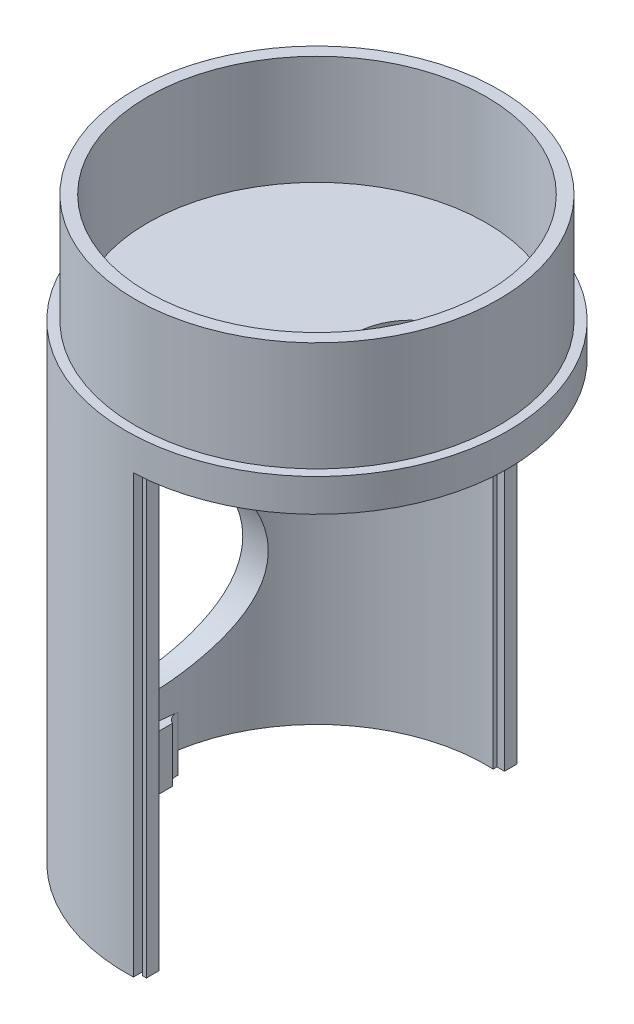
SolidWorks part; units mm, degrees
ref_plane "Front Plane" through (0, 0, 0) normal (0, 0, 1) x (1, 0, 0)
ref_plane "Top Plane" through (0, 0, 0) normal (0, 1, 0) x (1, 0, 0)
ref_plane "Right Plane" through (0, 0, 0) normal (1, 0, 0) x (0, 0, -1)
sketch "Sketch13" plane through (0, 0, 0) normal (0, 1, 0) x (1, 0, 0)
  line L0 (0, 0) -> (-19.6145, 0) construction
  line L28 (0.6552, 15.4861) -> (0.6552, 15.8306)
  line L29 (0.6552, 15.8306) -> (1.3406, 15.8306)
  line L30 (1.3406, 15.8306) -> (1.343, 16.9583)
  line L31 (1.343, 16.9583) -> (0.9998, 16.9583)
  line L32 (0.9998, 16.9583) -> (0.9998, 16.6614)
  line L33 (0.9998, 16.6614) -> (0.6704, 16.6614)
  line L34 (0.6704, 16.6614) -> (0.6704, 17.4872)
  line L35 (0.6704, -17.4872) -> (0.6704, -16.6614)
  line L36 (0.6704, -16.6614) -> (0.9998, -16.6614)
  line L37 (0.9998, -16.6614) -> (0.9998, -16.9583)
  line L38 (0.9998, -16.9583) -> (1.343, -16.9583)
  line L39 (1.343, -16.9583) -> (1.3406, -15.8306)
  line L40 (1.3406, -15.8306) -> (0.6552, -15.8306)
  line L41 (0.6552, -15.8306) -> (0.6552, -15.4861)
  arc A4 (0.6704, 17.4872) -> (0.6704, -17.4872) centre (0, 0) ccw
  arc A5 (0.6552, 15.4861) -> (0.6552, -15.4861) centre (0, 0) ccw
extrude "Boss-Extrude1" add sketch "Sketch13" along normal blind 40
sketch "Sketch16" plane through (0, 40, 0) normal (0, 1, 0) x (1, 0, 0)
  circle A0 centre (0, 0) radius 17.5
  dimension "D1" = 35
extrude "Boss-Extrude2" add sketch "Sketch16" along normal blind 3
sketch "Sketch17" plane through (0, 43, 0) normal (0, 1, 0) x (1, 0, 0)
  circle A0 centre (0, 0) radius 16.65
  circle A1 centre (0, 0) radius 15.5
  point P3 (0, 0)
  dimension "D2" = 31
  dimension "D1" = 33.3
extrude "Boss-Extrude3" add sketch "Sketch17" along normal blind 10
sketch "Sketch18" plane through (0, 0, 0) normal (1, 0, 0) x (0, 0, -1)
  circle A0 centre (0, 14) radius 8.5
  dimension "D1" = 14
  dimension "D2" = 17
extrude "Cut-Extrude1" cut sketch "Sketch18" against normal blind 30 contours A0
sketch "Sketch20" plane through (0, 0, 0) normal (0, -1, 0) x (1, 0, 0)
  line L0 (-14.6678, 1.4488) -> (-14.6678, -1.4488)
  arc A0 (-15.41, 1.6684) -> (-14.6678, 1.4488) centre (-15.5, 0) cw
  arc A1 (0.6552, 15.4861) -> (0.6552, -15.4861) centre (0, 0) ccw construction
  arc A2 (-14.6678, -1.4488) -> (-15.41, -1.6684) centre (-15.5, 0) cw
  arc A3 (-15.41, 1.6684) -> (-15.41, -1.6684) centre (0, 0) ccw
  point P5 (0, 0)
  point P9 (0, 0)
  point P10 (0, 0)
extrude "Boss-Extrude4" add sketch "Sketch20" against normal blind 3
fillet "Fillet1" radius 1 1 edges at (-15.41, 1.5, 1.6684)
fillet "Fillet3" radius 1 1 edges at (-15.41, 1.5, -1.6684)
sketch "Sketch25" plane through (0, 0, 0) normal (0, -1, 0) x (1, 0, 0)
  line L0 (-15.5, 2.5605) -> (-15.5, -2.5605)
  line L15 (0.6552, 15.4861) -> (0.6552, 15.8306)
  line L16 (0.6552, 15.8306) -> (1.3406, 15.8306)
  line L17 (1.3406, 15.8306) -> (1.343, 16.9583)
  line L18 (1.343, 16.9583) -> (0.9998, 16.9583)
  line L19 (0.9998, 16.9583) -> (0.9998, 16.6614)
  line L20 (0.9998, 16.6614) -> (0.6704, 16.6614)
  line L21 (0.6704, 16.6614) -> (0.6704, 17.4872)
  line L22 (0.6704, -17.4872) -> (0.6704, -16.6614)
  line L23 (0.6704, -16.6614) -> (0.9998, -16.6614)
  line L24 (0.9998, -16.6614) -> (0.9998, -16.9583)
  line L25 (0.9998, -16.9583) -> (1.343, -16.9583)
  line L26 (1.343, -16.9583) -> (1.3406, -15.8306)
  line L27 (1.3406, -15.8306) -> (0.6552, -15.8306)
  line L28 (0.6552, -15.8306) -> (0.6552, -15.4861)
  line L29 (-14.6678, -1.4488) -> (-14.6678, 1.4488)
  line L44 (-14.6678, -1.4488) -> (-14.6678, 1.4488)
  arc A0 (-15.2885, 2.5517) -> (-15.5, 2.5605) centre (-15.5, 0) ccw
  arc A1 (-15.5, -2.5605) -> (-15.2885, -2.5517) centre (-15.5, 0) ccw
  arc A7 (0.6552, 15.4861) -> (-15.2885, 2.5517) centre (0, 0) ccw
  arc A8 (0.6704, 17.4872) -> (0.6704, -17.4872) centre (0, 0) ccw
  arc A9 (-15.2885, -2.5517) -> (0.6552, -15.4861) centre (0, 0) ccw
  arc A10 (-14.7507, -1.4933) -> (-15.2885, -2.5517) centre (-14.3022, -2.3871) ccw
  arc A11 (-14.7507, -1.4933) -> (-14.6678, -1.4488) centre (-15.5, 0) ccw
  arc A12 (-14.6678, 1.4488) -> (-14.7507, 1.4933) centre (-15.5, 0) ccw
  arc A13 (-15.2885, 2.5517) -> (-14.7507, 1.4933) centre (-14.3022, 2.3871) ccw
  arc A17 (-14.7507, -1.4933) -> (-15.2885, -2.5517) centre (-14.3022, -2.3871) ccw
  arc A18 (-14.7507, -1.4933) -> (-14.6678, -1.4488) centre (-15.5, 0) ccw
  arc A19 (-14.6678, 1.4488) -> (-14.7507, 1.4933) centre (-15.5, 0) ccw
  arc A20 (-15.2885, 2.5517) -> (-14.7507, 1.4933) centre (-14.3022, 2.3871) ccw
  dimension "D1" = 0
extrude "Boss-Extrude5" add sketch "Sketch25" along normal blind 2
sketch "Sketch27" plane through (0, -2, 0) normal (0, -1, 0) x (1, 0, 0)
  line L0 (-15.2885, 2.5517) -> (-15.5, 1.1365)
  line L1 (-15.5, 2.5605) -> (-15.5, -2.5605) construction
  line L2 (-15.5, 1.1365) -> (-15.5, -1.2382)
  line L3 (-15.5, -1.2382) -> (-15.2885, -2.5517)
extrude "Cut-Extrude3" cut sketch "Sketch27" against normal blind 2 and the other way through all flip side to cut
sketch "Sketch28" plane through (0, 43, 0) normal (0, 1, 0) x (1, 0, 0)
  circle A0 centre (7.8255, 0.7368) radius 5.0511
extrude "Cut-Extrude4" cut sketch "Sketch28" against normal blind 10
